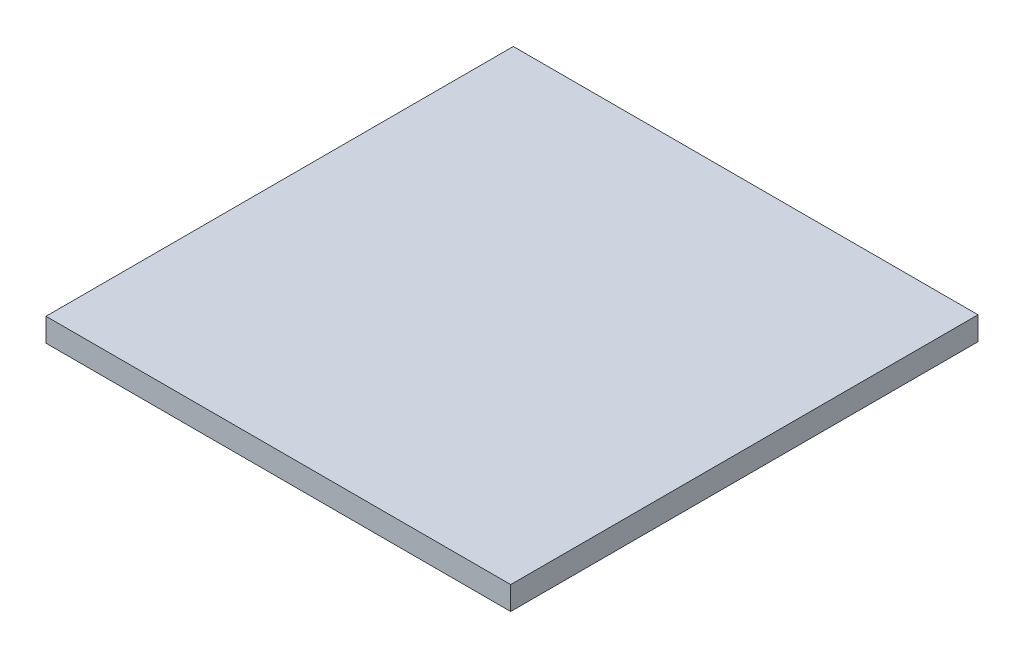
SolidWorks part; units mm, degrees
ref_plane "Alzado" through (0, 0, 0) normal (0, 0, 1) x (1, 0, 0)
ref_plane "Planta" through (0, 0, 0) normal (0, 1, 0) x (1, 0, 0)
ref_plane "Vista lateral" through (0, 0, 0) normal (1, 0, 0) x (0, 0, -1)
sketch "Croquis1" plane through (0, 0, 0) normal (0, 1, 0) x (1, 0, 0)
  line L1 (-179, 180) -> (179, 180)
  line L2 (-179, 180) -> (-179, -180)
  line L3 (-179, -180) -> (179, -180)
  line L4 (179, 180) -> (179, -180)
  line L5 (-179, 180) -> (179, -180) construction
  line L6 (-179, -180) -> (179, 180) construction
  point P0 (0, 0)
  dimension "D1" = 358
  dimension "D2" = 360
extrude "Saliente-Extruir1" add sketch "Croquis1" along normal blind 18
